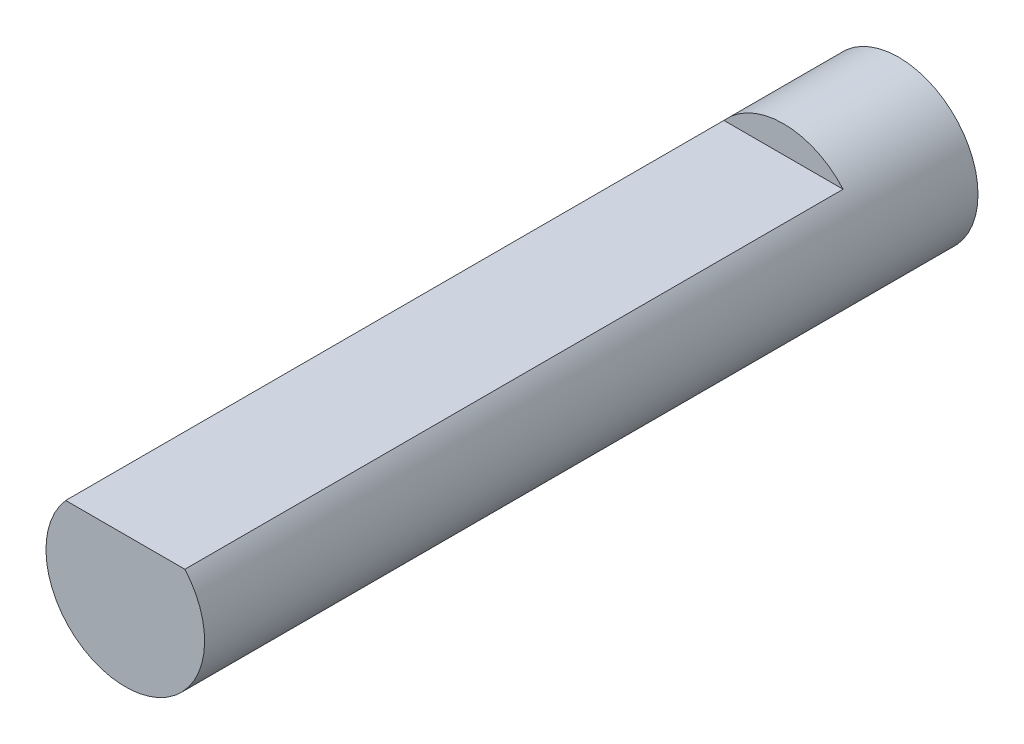
SolidWorks part; units mm, degrees
ref_plane "Front Plane" through (0, 0, 0) normal (0, 0, 1) x (1, 0, 0)
ref_plane "Top Plane" through (0, 0, 0) normal (0, 1, 0) x (1, 0, 0)
ref_plane "Right Plane" through (0, 0, 0) normal (1, 0, 0) x (0, 0, -1)
sketch "Sketch1" plane through (0, 0, 0) normal (0, 0, 1) x (1, 0, 0)
  line L0 (-0.9055, 0.795) -> (0.9055, 0.795)
  line L1 (-3.6197, -1.205) -> (4.9029, -1.205) construction
  circle A0 centre (0, 0) radius 1.205
  dimension "D2" = 2.41
  dimension "D1" = 2
extrude "rod" add sketch "Sketch1" along normal blind 10 contours L0 A0 region at (0, -0.1223, 0)
extrude "Slot" add sketch "Sketch1<3>" against normal blind 1.75 contours L0 A0 | L0 A0 region at (0, 0.9617, 0) region at (0, -0.1223, 0)
sketch "Sketch1<3>" plane through (0, 0, 0) normal (0, 0, 1) x (1, 0, 0) same geometry as "Sketch1"
